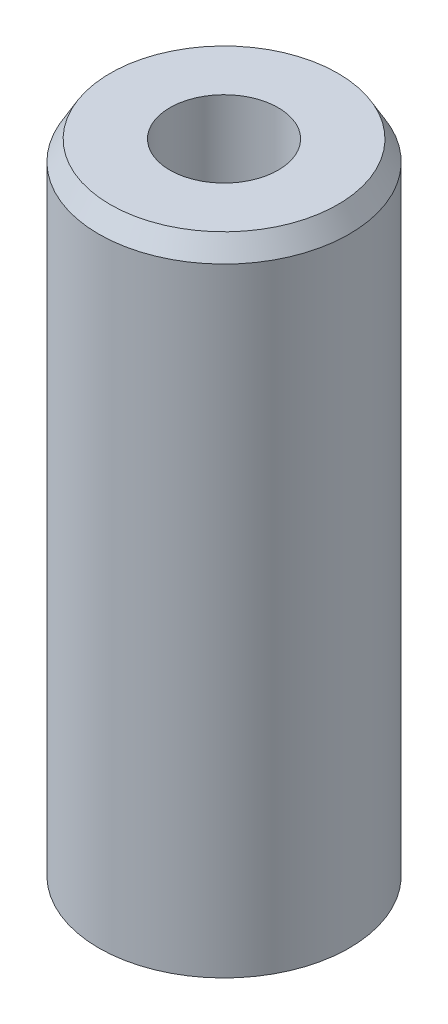
SolidWorks part; units mm, degrees
ref_plane "Front Plane" through (0, 0, 0) normal (0, 0, 1) x (1, 0, 0)
ref_plane "Top Plane" through (0, 0, 0) normal (0, 1, 0) x (1, 0, 0)
ref_plane "Right Plane" through (0, 0, 0) normal (1, 0, 0) x (0, 0, -1)
sketch "Sketch1" plane through (0, 0, 0) normal (0, 1, 0) x (1, 0, 0)
  circle A0 centre (0, 0) radius 10
  dimension "SHAFT_OD" = 20
extrude "Boss-Extrude1" add sketch "Sketch1" along normal blind 51.8531
sketch "Sketch2" plane through (0, 0, 0) normal (0, 1, 0) x (1, 0, 0)
  circle A0 centre (0, 0) radius 4.3234
  dimension "BORE_D" = 8.6468
extrude "Cut-Extrude1" cut sketch "Sketch2" along normal through all
chamfer "Chamfer1" distance 1.5848 angle 30 2 edges at (0, 51.8531, 10) (0, 0, 10) first distance on face at (0, 51.8531, 10) first distance on face at (0, 0, 4.3234)
